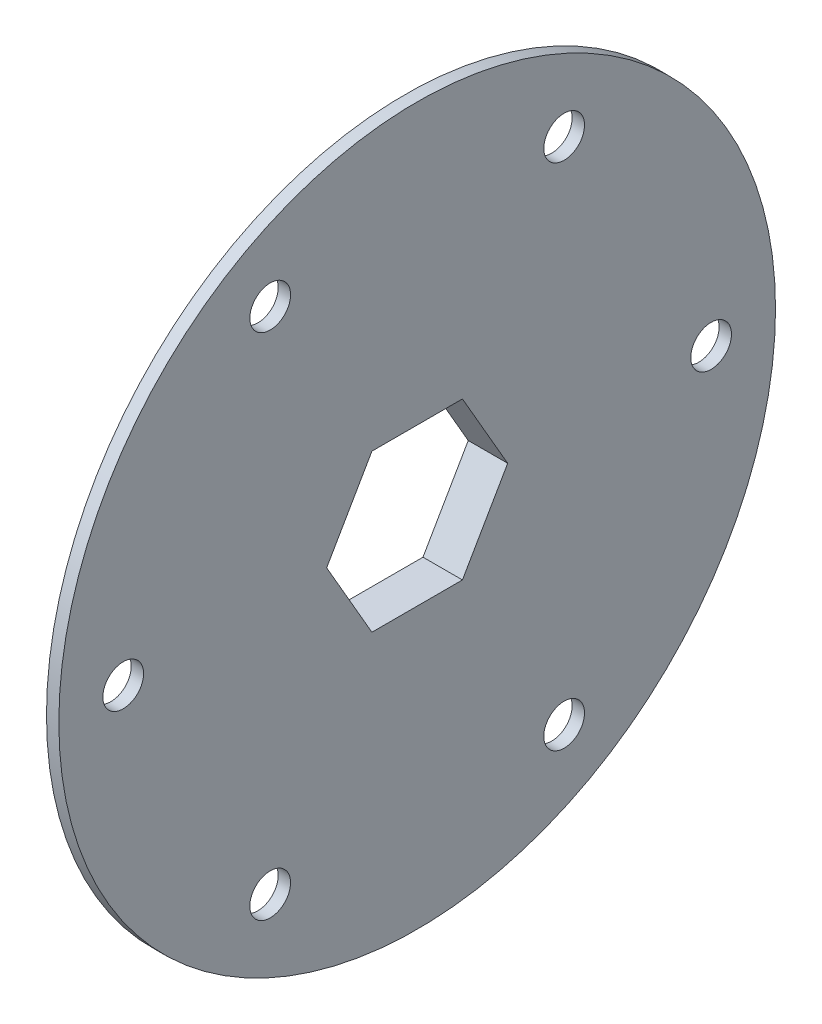
SolidWorks part; units mm, degrees
ref_plane "Front Plane" through (0, 0, 0) normal (0, 0, 1) x (1, 0, 0)
ref_plane "Top Plane" through (0, 0, 0) normal (0, 1, 0) x (1, 0, 0)
ref_plane "Right Plane" through (0, 0, 0) normal (1, 0, 0) x (0, 0, -1)
sketch "Sketch1" plane through (0, 0, 0) normal (1, 0, 0) x (0, 0, -1)
  line L1 (3.6662, 6.35) -> (-3.6662, 6.35)
  line L2 (-3.6662, 6.35) -> (-7.3323, 0)
  line L3 (-7.3323, 0) -> (-3.6662, -6.35)
  line L4 (-3.6662, -6.35) -> (3.6662, -6.35)
  line L5 (3.6662, -6.35) -> (7.3323, 0)
  line L6 (7.3323, 0) -> (3.6662, 6.35)
  circle A0 centre (0, 0) radius 29.03
  circle A1 centre (0, 0) radius 6.35 construction
  circle A2 centre (0, 0) radius 9
  circle A3 centre (11.9063, -20.6222) radius 1.65 construction
  circle A4 centre (23.8125, 0) radius 1.65 construction
  circle A5 centre (11.9063, 20.6222) radius 1.65 construction
  circle A6 centre (-11.9062, 20.6222) radius 1.65 construction
  circle A7 centre (-23.8125, 0) radius 1.65 construction
  circle A8 centre (-11.9062, -20.6222) radius 1.65 construction
  circle A9 centre (11.9063, -20.6222) radius 1.65
  circle A10 centre (23.8125, 0) radius 1.65
  circle A11 centre (11.9063, 20.6222) radius 1.65
  circle A12 centre (-11.9062, 20.6222) radius 1.65
  circle A13 centre (-23.8125, 0) radius 1.65
  circle A14 centre (-11.9062, -20.6222) radius 1.65
  dimension "D1" = 58.06
  dimension "D3" = 18
  dimension "D2" = 12.7
extrude "Boss-Extrude1" add sketch "Sketch1" along normal blind 1 contours A0 A2 | A2 L6 L5 L4 L3 L2 L1 region at (0, 0, 28.2089) region at (0, 0, 8.7454)
extrude "Boss-Extrude2" add sketch "Sketch1<3>" against normal up to surface (2.1954 mm away) contours L5 L6 L1 L2 L3 L4 | A2 region at (0, 0, 0)
sketch "Sketch1<3>" plane through (0, 0, 0) normal (1, 0, 0) x (0, 0, -1) same geometry as "Sketch1"
fillet "Fillet1" radius 5 1 edges at (0, 0, -9)
